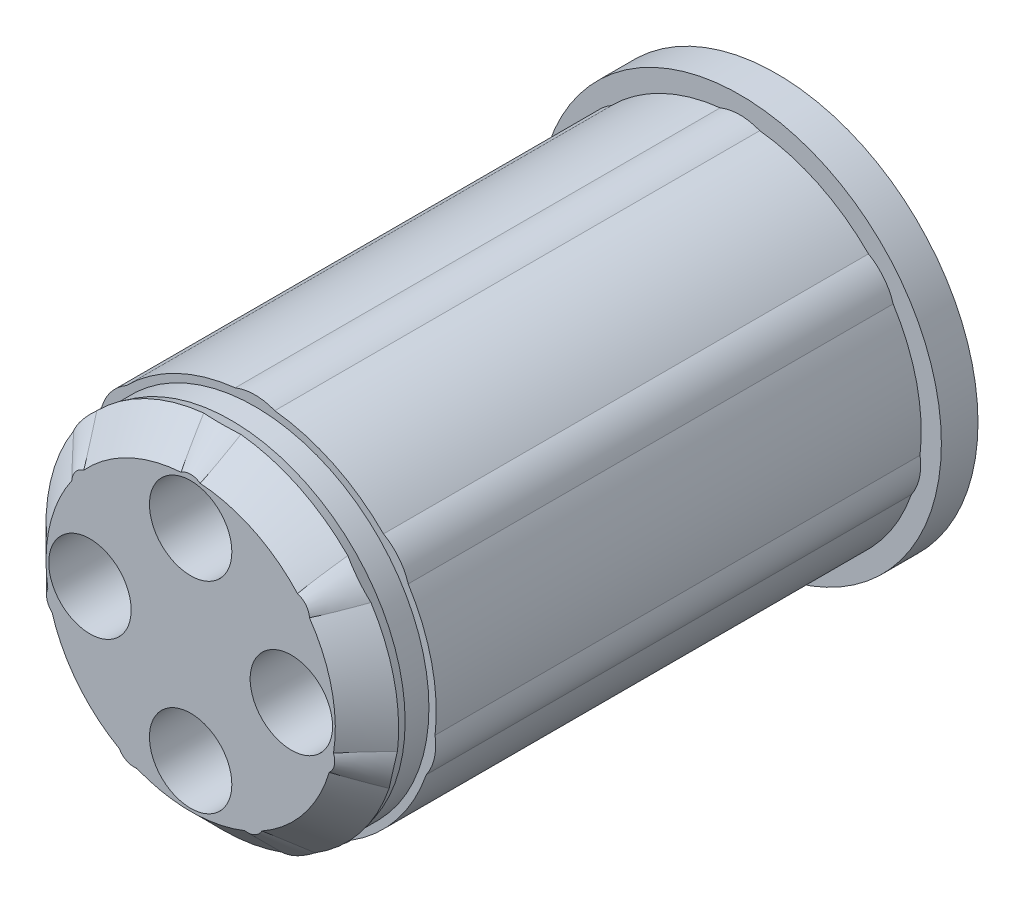
SolidWorks part; units mm, degrees
ref_plane "Ebene vorne" through (0, 0, 0) normal (0, 0, 1) x (1, 0, 0)
ref_plane "Ebene oben" through (0, 0, 0) normal (0, 1, 0) x (1, 0, 0)
ref_plane "Ebene rechts" through (0, 0, 0) normal (1, 0, 0) x (0, 0, -1)
sketch "Skizze1" plane through (0, 0, 0) normal (0, 0, 1) x (1, 0, 0)
  line L0 (0, 0) -> (0, 7.15) construction
  circle A0 centre (0, 0) radius 9.9
  circle A1 centre (0, 0) radius 10.05 construction
  circle A2 centre (0, 7.15) radius 2.9
  circle A7 centre (5.5901, 4.458) radius 2.9
  circle A8 centre (6.9707, -1.591) radius 2.9
  circle A9 centre (3.1023, -6.4419) radius 2.9
  circle A10 centre (-3.1023, -6.4419) radius 2.9
  circle A11 centre (-6.9707, -1.591) radius 2.9
  circle A12 centre (-5.5901, 4.458) radius 2.9
  point P17 (0, 0)
  point P21 (0, 0)
  dimension "D1" = 19.8
  dimension "D2" = 20.1
  dimension "D3" = 5.8
  dimension "D4" = 7
extrude "Aufsatz-Linear austragen1" add sketch "Skizze1" along normal blind 32 contours A0 A12 | A0 A2 | A0 A7 | A0 A8 | A0 A9 | A0 A10 | A0 A11 | A0 A11 | A0 A12 | A0 A2 | A0 A8 | A0 A9 | A0 A10 | A12 A0 A11 A10 A9 A8 A7 A2 | A0 A7 region at (0, 0, 0) region at (5.5718, 4.4434, 0) region at (7.7779, 6.2027, 0) region at (9.6989, -2.2137, 0) region at (6.948, -1.5858, 0) region at (0, 7.1267, 0) region at (0, 9.9483, 0) region at (4.3164, -8.9631, 0) region at (3.0921, -6.4209, 0) region at (-5.5718, 4.4434, 0) region at (-7.7779, 6.2027, 0) region at (-4.3164, -8.9631, 0) region at (-3.0921, -6.4209, 0) region at (-6.948, -1.5858, 0) region at (-9.6989, -2.2137, 0)
sketch "Skizze2" plane through (0, 0, 0) normal (0, 0, 1) x (1, 0, 0)
  circle A0 centre (0, 0) radius 11
  dimension "D1" = 22
extrude "Aufsatz-Linear austragen2" add sketch "Skizze2" along normal blind 2
chamfer "Fase1" distance 2 angle 45 14 edges at (9.798, -2.2363, 32) (7.7401, -6.1725, 32) (4.3605, -9.0547, 32) (0, -9.9, 32) (-4.3605, -9.0547, 32) (-7.7401, -6.1725, 32) (-9.798, -2.2363, 32) (-9.6518, 2.203, 32) (-7.8574, 6.2661, 32) (-4.2954, 8.9196, 32) (0, 10.05, 32) (4.2954, 8.9196, 32) (7.8574, 6.2661, 32) (9.6518, 2.203, 32)
sketch "Skizze3" plane through (0, 0, 2) normal (0, 0, 1) x (1, 0, 0)
  line L0 (0, 0) -> (0, 5.5) construction
  circle A0 centre (0, 0) radius 5.5 construction
  circle A1 centre (0, 5.5) radius 2.25
  circle A2 centre (5.5, 0) radius 2.25
  circle A3 centre (0, -5.5) radius 2.25
  circle A4 centre (-5.5, 0) radius 2.25
  point P14 (0, 0)
  dimension "D1" = 5.5
  dimension "D2" = 4.5
  dimension "D3" = 4
extrude "Schnitt-Linear austragen1" cut sketch "Skizze3" against normal through all and the other way through all
sketch "Skizze4" plane through (0, 0, 0) normal (1, 0, 0) x (0, 0, -1)
  line L0 (-2, 10.05) -> (-30, 10.05) construction
  line L1 (-29.7861, 10.05) -> (-28.4861, 10.05)
  line L2 (-29.7861, 10.05) -> (-29.7861, 9.5) construction
  line L3 (-29.7861, 9.5) -> (-28.4861, 9.5)
  line L4 (-28.4861, 10.05) -> (-28.4861, 9.5)
  line L5 (-29.7861, 9.5) -> (-31.8388, 10.05)
  line L6 (0, 0) -> (3.3435, 0) construction
  line L8 (-28.1861, 13.3) -> (-28.1861, -13.3) construction
  line L10 (-31.8388, 10.05) -> (-29.7861, 10.05)
  point P6 (-28.6483, 9.5)
  dimension "D1" = 0.3
  dimension "D2" = 19
  dimension "D3" = 1.3
  dimension "D4" = 75
revolve "Schnitt-Rotation1" cut sketch "Skizze4" angle 360 about L6
ref_axis "Achse1" through (0, 0, -1.5) along (0, 0, 1)
